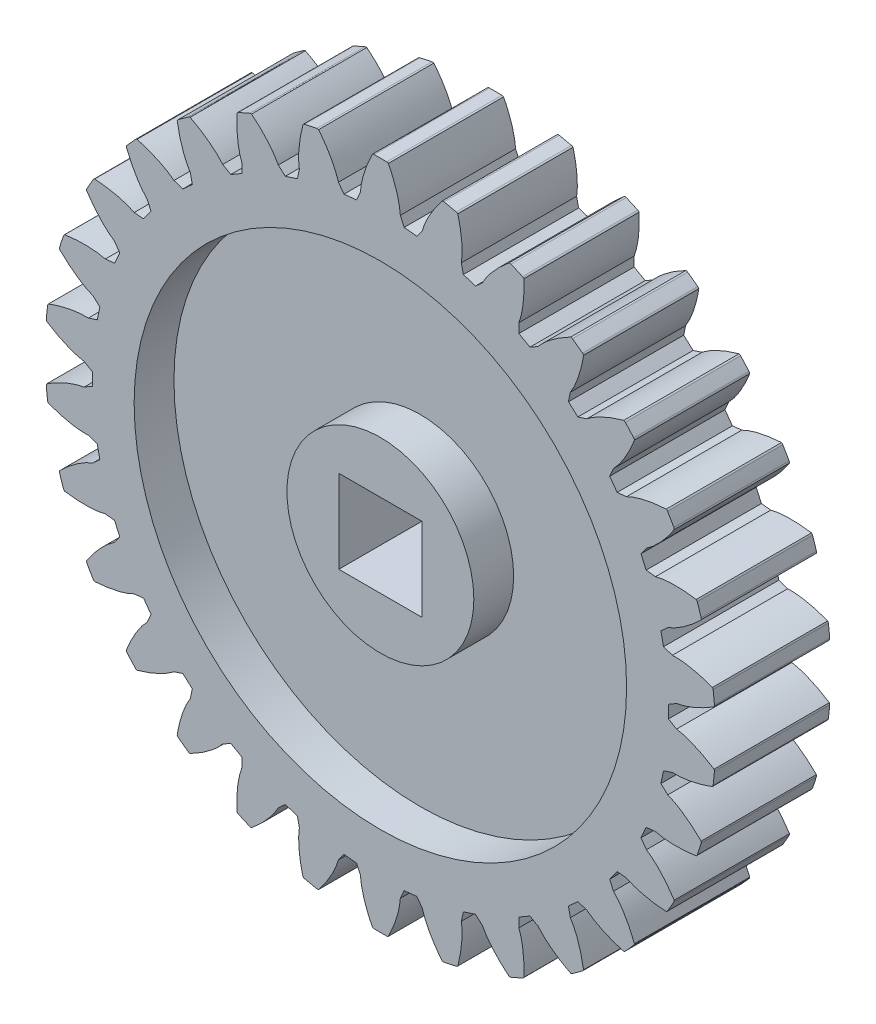
SolidWorks part; units mm, degrees
material "Nylon 101"
ref_plane "Front Plane" through (0, 0, 0) normal (0, 0, 1) x (1, 0, 0)
ref_plane "Top Plane" through (0, 0, 0) normal (0, 1, 0) x (1, 0, 0)
ref_plane "Right Plane" through (0, 0, 0) normal (1, 0, 0) x (0, 0, -1)
ref_axis "Axis1" through (0, 0, -3.2875) along (0, 0, 1)
sketch "Sketch1" plane through (0, 0, 0) normal (0, 0, 1) x (1, 0, 0)
  arc A0 (3.6196, 15.5852) -> (3.0324, 15.71) centre (0, 0) ccw
  arc A1 (0.3001, 15.9972) -> (-0.3001, 15.9972) centre (0, 0) ccw
  arc A2 (-3.0324, 15.71) -> (-3.6196, 15.5852) centre (0, 0) ccw
  arc A3 (-6.2325, 14.7362) -> (-6.7808, 14.4921) centre (0, 0) ccw
  arc A4 (-9.1601, 13.1184) -> (-9.6457, 12.7656) centre (0, 0) ccw
  arc A5 (-11.6874, 10.9272) -> (-12.089, 10.4812) centre (0, 0) ccw
  arc A6 (-13.7039, 8.2585) -> (-14.004, 7.7387) centre (0, 0) ccw
  arc A7 (-15.1215, 5.2288) -> (-15.307, 4.658) centre (0, 0) ccw
  arc A8 (-15.8782, 1.9706) -> (-15.9409, 1.3737) centre (0, 0) ccw
  arc A9 (-15.9409, -1.3737) -> (-15.8782, -1.9706) centre (0, 0) ccw
  arc A10 (-15.307, -4.658) -> (-15.1215, -5.2288) centre (0, 0) ccw
  arc A11 (-14.004, -7.7387) -> (-13.7039, -8.2585) centre (0, 0) ccw
  arc A12 (-12.089, -10.4812) -> (-11.6874, -10.9272) centre (0, 0) ccw
  arc A13 (-9.6457, -12.7656) -> (-9.1601, -13.1184) centre (0, 0) ccw
  arc A14 (-6.7808, -14.4921) -> (-6.2325, -14.7362) centre (0, 0) ccw
  arc A15 (-3.6196, -15.5852) -> (-3.0324, -15.71) centre (0, 0) ccw
  arc A16 (-0.3001, -15.9972) -> (0.3001, -15.9972) centre (0, 0) ccw
  arc A17 (3.0324, -15.71) -> (3.6196, -15.5852) centre (0, 0) ccw
  arc A18 (6.2325, -14.7362) -> (6.7808, -14.4921) centre (0, 0) ccw
  arc A19 (9.1601, -13.1184) -> (9.6457, -12.7656) centre (0, 0) ccw
  arc A20 (11.6874, -10.9272) -> (12.089, -10.4812) centre (0, 0) ccw
  arc A21 (13.7039, -8.2585) -> (14.004, -7.7387) centre (0, 0) ccw
  arc A22 (15.1215, -5.2288) -> (15.307, -4.658) centre (0, 0) ccw
  arc A23 (15.8782, -1.9706) -> (15.9409, -1.3737) centre (0, 0) ccw
  arc A24 (15.9409, 1.3737) -> (15.8782, 1.9706) centre (0, 0) ccw
  arc A25 (15.307, 4.658) -> (15.1215, 5.2288) centre (0, 0) ccw
  arc A26 (14.004, 7.7387) -> (13.7039, 8.2585) centre (0, 0) ccw
  arc A27 (12.089, 10.4812) -> (11.6874, 10.9272) centre (0, 0) ccw
  arc A28 (9.6457, 12.7656) -> (9.1601, 13.1184) centre (0, 0) ccw
  arc A29 (6.7808, 14.4921) -> (6.2325, 14.7362) centre (0, 0) ccw
  spline S0 degree 2 poles (3.6196, 15.5852) (3.6647, 15.5747) (3.6932, 15.5435) knots 0 0 0 1 1 1
  spline S1 degree 2 poles (2.9482, 15.7019) (2.9869, 15.7188) (3.0324, 15.71) knots 0 0 0 1 1 1
  spline S2 degree 2 poles (2.0027, 14.0013) (2.021, 14.0609) (2.0394, 14.1205) (2.1444, 14.4615) (2.6134, 15.2842) (2.9482, 15.7019) knots -0.082148 -0.082148 -0.082148 0 0 0.469989 0.94695 0.94695 0.94695
  spline S3 degree 2 poles (1.7379, 13.6408) (1.799, 13.7255) (1.8601, 13.8102) (1.9057, 13.8734) (1.9535, 13.9364) (1.9781, 13.9689) (2.0027, 14.0013) knots -1.340212 -1.340212 -1.340212 0 0 1 1 1.515233 1.515233 1.515233
  spline S4 degree 2 poles (1.1362, 13.7041) (1.2218, 13.6959) (1.3075, 13.6877) (1.4373, 13.6753) (1.5669, 13.6604) (1.6524, 13.6506) (1.7379, 13.6408) knots -0.659931 -0.659931 -0.659931 0 0 1 1 1.659931 1.659931 1.659931
  spline S5 degree 2 poles (0.9521, 14.1118) (0.9694, 14.0749) (0.9867, 14.038) (1.0203, 13.9665) (1.0518, 13.8952) (1.094, 13.7996) (1.1362, 13.7041) knots -0.515233 -0.515233 -0.515233 0 0 1 1 2.340212 2.340212 2.340212
  spline S6 degree 2 poles (0.3808, 15.9717) (0.7214, 15.2951) (0.9228, 14.4394) (0.941, 14.236) (0.9466, 14.1739) (0.9521, 14.1118) knots 0 0 0 0.627513 0.879079 0.879079 0.955892 0.955892 0.955892
  spline S7 degree 2 poles (0.3001, 15.9972) (0.3465, 15.9963) (0.3808, 15.9717) knots 0 0 0 1 1 1
  spline S8 degree 2 poles (-0.3808, 15.9717) (-0.3465, 15.9963) (-0.3001, 15.9972) knots 0 0 0 1 1 1
  spline S9 degree 2 poles (-0.9521, 14.1118) (-0.9466, 14.1739) (-0.941, 14.236) (-0.9092, 14.5914) (-0.6215, 15.4935) (-0.3808, 15.9717) knots -0.082148 -0.082148 -0.082148 0 0 0.469989 0.94695 0.94695 0.94695
  spline S10 degree 2 poles (-1.1362, 13.7041) (-1.094, 13.7996) (-1.0518, 13.8952) (-1.0203, 13.9665) (-0.9867, 14.038) (-0.9694, 14.0749) (-0.9521, 14.1118) knots -1.340212 -1.340212 -1.340212 0 0 1 1 1.515233 1.515233 1.515233
  spline S11 degree 2 poles (-1.7379, 13.6408) (-1.6524, 13.6506) (-1.5669, 13.6604) (-1.4373, 13.6753) (-1.3075, 13.6877) (-1.2218, 13.6959) (-1.1362, 13.7041) knots -0.659931 -0.659931 -0.659931 0 0 1 1 1.659931 1.659931 1.659931
  spline S12 degree 2 poles (-2.0027, 14.0013) (-1.9781, 13.9689) (-1.9535, 13.9364) (-1.9057, 13.8734) (-1.8601, 13.8102) (-1.799, 13.7255) (-1.7379, 13.6408) knots -0.515233 -0.515233 -0.515233 0 0 1 1 2.340212 2.340212 2.340212
  spline S13 degree 2 poles (-2.9482, 15.7019) (-2.4744, 15.1108) (-2.0995, 14.3157) (-2.0394, 14.1205) (-2.021, 14.0609) (-2.0027, 14.0013) knots 0 0 0 0.627513 0.879079 0.879079 0.955892 0.955892 0.955892
  spline S14 degree 2 poles (-3.0324, 15.71) (-2.9869, 15.7188) (-2.9482, 15.7019) knots 0 0 0 1 1 1
  spline S15 degree 2 poles (-3.6932, 15.5435) (-3.6647, 15.5747) (-3.6196, 15.5852) knots 0 0 0 1 1 1
  spline S16 degree 2 poles (-3.8653, 13.6054) (-3.8728, 13.6673) (-3.8803, 13.7292) (-3.923, 14.0835) (-3.8292, 15.0258) (-3.6932, 15.5435) knots -0.082148 -0.082148 -0.082148 0 0 0.469989 0.94695 0.94695 0.94695
  spline S17 degree 2 poles (-3.9606, 13.1684) (-3.9392, 13.2706) (-3.9178, 13.3728) (-3.9018, 13.4491) (-3.8839, 13.5261) (-3.8746, 13.5658) (-3.8653, 13.6054) knots -1.340212 -1.340212 -1.340212 0 0 1 1 1.515233 1.515233 1.515233
  spline S18 degree 2 poles (-4.536, 12.9814) (-4.4544, 13.0088) (-4.3728, 13.0361) (-4.2492, 13.0776) (-4.1248, 13.1167) (-4.0427, 13.1426) (-3.9606, 13.1684) knots -0.659931 -0.659931 -0.659931 0 0 1 1 1.659931 1.659931 1.659931
  spline S19 degree 2 poles (-4.87, 13.279) (-4.8392, 13.2524) (-4.8083, 13.2257) (-4.7485, 13.174) (-4.6908, 13.1217) (-4.6134, 13.0515) (-4.536, 12.9814) knots -0.515233 -0.515233 -0.515233 0 0 1 1 2.340212 2.340212 2.340212
  spline S20 degree 2 poles (-6.1484, 14.7458) (-5.5621, 14.2662) (-5.03, 13.5664) (-4.9306, 13.388) (-4.9003, 13.3335) (-4.87, 13.279) knots 0 0 0 0.627513 0.879079 0.879079 0.955892 0.955892 0.955892
  spline S21 degree 2 poles (-6.2325, 14.7362) (-6.1897, 14.7543) (-6.1484, 14.7458) knots 0 0 0 1 1 1
  spline S22 degree 2 poles (-6.8442, 14.436) (-6.8228, 14.4724) (-6.7808, 14.4921) knots 0 0 0 1 1 1
  spline S23 degree 2 poles (-6.6096, 12.5045) (-6.6298, 12.5635) (-6.6499, 12.6225) (-6.7654, 12.9601) (-6.8695, 13.9013) (-6.8442, 14.436) knots -0.082148 -0.082148 -0.082148 0 0 0.469989 0.94695 0.94695 0.94695
  spline S24 degree 2 poles (-6.6119, 12.0572) (-6.6122, 12.1616) (-6.6126, 12.2661) (-6.6128, 12.344) (-6.6112, 12.423) (-6.6104, 12.4637) (-6.6096, 12.5045) knots -1.340212 -1.340212 -1.340212 0 0 1 1 1.515233 1.515233 1.515233
  spline S25 degree 2 poles (-7.1359, 11.7546) (-7.0617, 11.7984) (-6.9876, 11.8421) (-6.8753, 11.9084) (-6.7618, 11.9725) (-6.6868, 12.0148) (-6.6119, 12.0572) knots -0.659931 -0.659931 -0.659931 0 0 1 1 1.659931 1.659931 1.659931
  spline S26 degree 2 poles (-7.5244, 11.9763) (-7.4887, 11.9566) (-7.453, 11.937) (-7.3838, 11.8989) (-7.3164, 11.8597) (-7.2262, 11.8072) (-7.1359, 11.7546) knots -0.515233 -0.515233 -0.515233 0 0 1 1 2.340212 2.340212 2.340212
  spline S27 degree 2 poles (-9.0799, 13.1452) (-8.4066, 12.798) (-7.7407, 12.2241) (-7.6064, 12.0703) (-7.5654, 12.0233) (-7.5244, 11.9763) knots 0 0 0 0.627513 0.879079 0.879079 0.955892 0.955892 0.955892
  spline S28 degree 2 poles (-9.1601, 13.1184) (-9.1221, 13.145) (-9.0799, 13.1452) knots 0 0 0 1 1 1
  spline S29 degree 2 poles (-9.696, 12.6976) (-9.6827, 12.7376) (-9.6457, 12.7656) knots 0 0 0 1 1 1
  spline S30 degree 2 poles (-9.065, 10.857) (-9.097, 10.9105) (-9.129, 10.964) (-9.3121, 11.2702) (-9.6097, 12.1692) (-9.696, 12.6976) knots -0.082148 -0.082148 -0.082148 0 0 0.469989 0.94695 0.94695 0.94695
  spline S31 degree 2 poles (-8.9742, 10.419) (-8.9963, 10.5211) (-9.0183, 10.6232) (-9.0348, 10.6994) (-9.0496, 10.777) (-9.0573, 10.817) (-9.065, 10.857) knots -1.340212 -1.340212 -1.340212 0 0 1 1 1.515233 1.515233 1.515233
  spline S32 degree 2 poles (-9.4239, 10.0141) (-9.3605, 10.0723) (-9.297, 10.1305) (-9.201, 10.2187) (-9.1032, 10.305) (-9.0387, 10.362) (-8.9742, 10.419) knots -0.659931 -0.659931 -0.659931 0 0 1 1 1.659931 1.659931 1.659931
  spline S33 degree 2 poles (-9.85, 10.1502) (-9.811, 10.1384) (-9.772, 10.1266) (-9.6964, 10.1037) (-9.6223, 10.0793) (-9.5231, 10.0467) (-9.4239, 10.0141) knots -0.515233 -0.515233 -0.515233 0 0 1 1 2.340212 2.340212 2.340212
  spline S34 degree 2 poles (-11.6145, 10.9702) (-10.8838, 10.7705) (-10.1131, 10.3476) (-9.9497, 10.225) (-9.8999, 10.1876) (-9.85, 10.1502) knots 0 0 0 0.627513 0.879079 0.879079 0.955892 0.955892 0.955892
  spline S35 degree 2 poles (-11.6874, 10.9272) (-11.6557, 10.9611) (-11.6145, 10.9702) knots 0 0 0 1 1 1
  spline S36 degree 2 poles (-12.1241, 10.4042) (-12.1194, 10.4461) (-12.089, 10.4812) knots 0 0 0 1 1 1
  spline S37 degree 2 poles (-11.1242, 8.735) (-11.1666, 8.7807) (-11.209, 8.8264) (-11.4519, 9.0879) (-11.9298, 9.9053) (-12.1241, 10.4042) knots -0.082148 -0.082148 -0.082148 0 0 0.469989 0.94695 0.94695 0.94695
  spline S38 degree 2 poles (-10.9443, 8.3255) (-10.9871, 8.4207) (-11.0299, 8.516) (-11.0619, 8.5871) (-11.0925, 8.66) (-11.1084, 8.6975) (-11.1242, 8.735) knots -1.340212 -1.340212 -1.340212 0 0 1 1 1.515233 1.515233 1.515233
  spline S39 degree 2 poles (-11.3, 7.836) (-11.2501, 7.9061) (-11.2001, 7.9762) (-11.1245, 8.0824) (-11.0468, 8.1872) (-10.9956, 8.2563) (-10.9443, 8.3255) knots -0.659931 -0.659931 -0.659931 0 0 1 1 1.659931 1.659931 1.659931
  spline S40 degree 2 poles (-11.7451, 7.8804) (-11.7045, 7.877) (-11.6639, 7.8736) (-11.5851, 7.8669) (-11.5077, 7.8585) (-11.4038, 7.8472) (-11.3, 7.836) knots -0.515233 -0.515233 -0.515233 0 0 1 1 2.340212 2.340212 2.340212
  spline S41 degree 2 poles (-13.6415, 8.3157) (-12.8853, 8.2723) (-12.0435, 8.0189) (-11.8582, 7.9329) (-11.8016, 7.9067) (-11.7451, 7.8804) knots 0 0 0 0.627513 0.879079 0.879079 0.955892 0.955892 0.955892
  spline S42 degree 2 poles (-13.7039, 8.2585) (-13.68, 8.2982) (-13.6415, 8.3157) knots 0 0 0 1 1 1
  spline S43 degree 2 poles (-14.0223, 7.6561) (-14.0265, 7.6981) (-14.004, 7.7387) knots 0 0 0 1 1 1
  spline S44 degree 2 poles (-12.6972, 6.2313) (-12.7482, 6.2672) (-12.7992, 6.3031) (-13.0911, 6.5083) (-13.7285, 7.2085) (-14.0223, 7.6561) knots -0.082148 -0.082148 -0.082148 0 0 0.469989 0.94695 0.94695 0.94695
  spline S45 degree 2 poles (-12.4361, 5.8681) (-12.4978, 5.9524) (-12.5595, 6.0367) (-12.6055, 6.0996) (-12.6507, 6.1645) (-12.6739, 6.1979) (-12.6972, 6.2313) knots -1.340212 -1.340212 -1.340212 0 0 1 1 1.515233 1.515233 1.515233
  spline S46 degree 2 poles (-12.6822, 5.3153) (-12.648, 5.3943) (-12.6137, 5.4732) (-12.5618, 5.5929) (-12.5076, 5.7115) (-12.4719, 5.7898) (-12.4361, 5.8681) knots -0.659931 -0.659931 -0.659931 0 0 1 1 1.659931 1.659931 1.659931
  spline S47 degree 2 poles (-13.1269, 5.2663) (-13.0864, 5.2714) (-13.046, 5.2764) (-12.9676, 5.2863) (-12.8901, 5.2942) (-12.7861, 5.3048) (-12.6822, 5.3153) knots -0.515233 -0.515233 -0.515233 0 0 1 1 2.340212 2.340212 2.340212
  spline S48 degree 2 poles (-15.0723, 5.2977) (-14.3236, 5.4125) (-13.4475, 5.3396) (-13.2484, 5.2941) (-13.1876, 5.2802) (-13.1269, 5.2663) knots 0 0 0 0.627513 0.879079 0.879079 0.955892 0.955892 0.955892
  spline S49 degree 2 poles (-15.1215, 5.2288) (-15.1063, 5.2727) (-15.0723, 5.2977) knots 0 0 0 1 1 1
  spline S50 degree 2 poles (-15.3077, 4.5734) (-15.3205, 4.6136) (-15.307, 4.658) knots 0 0 0 1 1 1
  spline S51 degree 2 poles (-13.7153, 3.4553) (-13.7727, 3.4797) (-13.83, 3.5042) (-14.1582, 3.6443) (-14.9273, 4.1967) (-15.3077, 4.5734) knots -0.082148 -0.082148 -0.082148 0 0 0.469989 0.94695 0.94695 0.94695
  spline S52 degree 2 poles (-13.3844, 3.1542) (-13.4623, 3.2239) (-13.5401, 3.2935) (-13.5982, 3.3455) (-13.6559, 3.3995) (-13.6856, 3.4274) (-13.7153, 3.4553) knots -1.340212 -1.340212 -1.340212 0 0 1 1 1.515233 1.515233 1.515233
  spline S53 degree 2 poles (-13.5102, 2.5624) (-13.4931, 2.6468) (-13.476, 2.7311) (-13.4501, 2.8589) (-13.4218, 2.9862) (-13.4031, 3.0702) (-13.3844, 3.1542) knots -0.659931 -0.659931 -0.659931 0 0 1 1 1.659931 1.659931 1.659931
  spline S54 degree 2 poles (-13.9349, 2.422) (-13.8964, 2.4353) (-13.858, 2.4487) (-13.7833, 2.4747) (-13.7091, 2.4985) (-13.6097, 2.5305) (-13.5102, 2.5624) knots -0.515233 -0.515233 -0.515233 0 0 1 1 2.340212 2.340212 2.340212
  spline S55 degree 2 poles (-15.8444, 2.0482) (-15.1359, 2.3162) (-14.2639, 2.4271) (-14.0596, 2.4239) (-13.9973, 2.4229) (-13.9349, 2.422) knots 0 0 0 0.627513 0.879079 0.879079 0.955892 0.955892 0.955892
  spline S56 degree 2 poles (-15.8782, 1.9706) (-15.8725, 2.0167) (-15.8444, 2.0482) knots 0 0 0 1 1 1
  spline S57 degree 2 poles (-15.924, 1.2908) (-15.9449, 1.3275) (-15.9409, 1.3737) knots 0 0 0 1 1 1
  spline S58 degree 2 poles (-14.134, 0.5282) (-14.1952, 0.5402) (-14.2564, 0.5522) (-14.6065, 0.621) (-15.4736, 1.0014) (-15.924, 1.2908) knots -0.082148 -0.082148 -0.082148 0 0 0.469989 0.94695 0.94695 0.94695
  spline S59 degree 2 poles (-13.7477, 0.3025) (-13.8384, 0.3545) (-13.929, 0.4064) (-13.9966, 0.4451) (-14.0643, 0.486) (-14.0991, 0.5071) (-14.134, 0.5282) knots -1.340212 -1.340212 -1.340212 0 0 1 1 1.515233 1.515233 1.515233
  spline S60 degree 2 poles (-13.7477, -0.3025) (-13.7486, -0.2165) (-13.7494, -0.1304) (-13.7506, 0) (-13.7494, 0.1304) (-13.7486, 0.2165) (-13.7477, 0.3025) knots -0.659931 -0.659931 -0.659931 0 0 1 1 1.659931 1.659931 1.659931
  spline S61 degree 2 poles (-14.134, -0.5282) (-14.0991, -0.5071) (-14.0643, -0.486) (-13.9966, -0.4451) (-13.929, -0.4064) (-13.8384, -0.3545) (-13.7477, -0.3025) knots -0.515233 -0.515233 -0.515233 0 0 1 1 2.340212 2.340212 2.340212
  spline S62 degree 2 poles (-15.924, -1.2908) (-15.2867, -0.8814) (-14.4568, -0.5916) (-14.2564, -0.5522) (-14.1952, -0.5402) (-14.134, -0.5282) knots 0 0 0 0.627513 0.879079 0.879079 0.955892 0.955892 0.955892
  spline S63 degree 2 poles (-15.9409, -1.3737) (-15.9449, -1.3275) (-15.924, -1.2908) knots 0 0 0 1 1 1
  spline S64 degree 2 poles (-15.8444, -2.0482) (-15.8725, -2.0167) (-15.8782, -1.9706) knots 0 0 0 1 1 1
  spline S65 degree 2 poles (-13.9349, -2.422) (-13.9973, -2.4229) (-14.0596, -2.4239) (-14.4164, -2.4294) (-15.3437, -2.2376) (-15.8444, -2.0482) knots -0.082148 -0.082148 -0.082148 0 0 0.469989 0.94695 0.94695 0.94695
  spline S66 degree 2 poles (-13.5102, -2.5624) (-13.6097, -2.5305) (-13.7091, -2.4985) (-13.7833, -2.4747) (-13.858, -2.4487) (-13.8964, -2.4353) (-13.9349, -2.422) knots -1.340212 -1.340212 -1.340212 0 0 1 1 1.515233 1.515233 1.515233
  spline S67 degree 2 poles (-13.3844, -3.1542) (-13.4031, -3.0702) (-13.4218, -2.9862) (-13.4501, -2.8589) (-13.476, -2.7311) (-13.4931, -2.6468) (-13.5102, -2.5624) knots -0.659931 -0.659931 -0.659931 0 0 1 1 1.659931 1.659931 1.659931
  spline S68 degree 2 poles (-13.7153, -3.4553) (-13.6856, -3.4274) (-13.6559, -3.3995) (-13.5982, -3.3455) (-13.5401, -3.2935) (-13.4623, -3.2239) (-13.3844, -3.1542) knots -0.515233 -0.515233 -0.515233 0 0 1 1 2.340212 2.340212 2.340212
  spline S69 degree 2 poles (-15.3077, -4.5734) (-14.7694, -4.0404) (-14.0179, -3.5844) (-13.83, -3.5042) (-13.7727, -3.4797) (-13.7153, -3.4553) knots 0 0 0 0.627513 0.879079 0.879079 0.955892 0.955892 0.955892
  spline S70 degree 2 poles (-15.307, -4.658) (-15.3205, -4.6136) (-15.3077, -4.5734) knots 0 0 0 1 1 1
  spline S71 degree 2 poles (-15.0723, -5.2977) (-15.1063, -5.2727) (-15.1215, -5.2288) knots 0 0 0 1 1 1
  spline S72 degree 2 poles (-13.1269, -5.2663) (-13.1876, -5.2802) (-13.2484, -5.2941) (-13.5962, -5.3737) (-14.5432, -5.3788) (-15.0723, -5.2977) knots -0.082148 -0.082148 -0.082148 0 0 0.469989 0.94695 0.94695 0.94695
  spline S73 degree 2 poles (-12.6822, -5.3153) (-12.7861, -5.3048) (-12.8901, -5.2942) (-12.9676, -5.2863) (-13.046, -5.2764) (-13.0864, -5.2714) (-13.1269, -5.2663) knots -1.340212 -1.340212 -1.340212 0 0 1 1 1.515233 1.515233 1.515233
  spline S74 degree 2 poles (-12.4361, -5.8681) (-12.4719, -5.7898) (-12.5076, -5.7115) (-12.5618, -5.5929) (-12.6137, -5.4732) (-12.648, -5.3943) (-12.6822, -5.3153) knots -0.659931 -0.659931 -0.659931 0 0 1 1 1.659931 1.659931 1.659931
  spline S75 degree 2 poles (-12.6972, -6.2313) (-12.6739, -6.1979) (-12.6507, -6.1645) (-12.6055, -6.0996) (-12.5595, -6.0367) (-12.4978, -5.9524) (-12.4361, -5.8681) knots -0.515233 -0.515233 -0.515233 0 0 1 1 2.340212 2.340212 2.340212
  spline S76 degree 2 poles (-14.0223, -7.6561) (-13.6066, -7.0228) (-12.9663, -6.4205) (-12.7992, -6.3031) (-12.7482, -6.2672) (-12.6972, -6.2313) knots 0 0 0 0.627513 0.879079 0.879079 0.955892 0.955892 0.955892
  spline S77 degree 2 poles (-14.004, -7.7387) (-14.0265, -7.6981) (-14.0223, -7.6561) knots 0 0 0 1 1 1
  spline S78 degree 2 poles (-13.6415, -8.3157) (-13.68, -8.2982) (-13.7039, -8.2585) knots 0 0 0 1 1 1
  spline S79 degree 2 poles (-11.7451, -7.8804) (-11.8016, -7.9067) (-11.8582, -7.9329) (-12.1819, -8.0831) (-13.1071, -8.285) (-13.6415, -8.3157) knots -0.082148 -0.082148 -0.082148 0 0 0.469989 0.94695 0.94695 0.94695
  spline S80 degree 2 poles (-11.3, -7.836) (-11.4038, -7.8472) (-11.5077, -7.8585) (-11.5851, -7.8669) (-11.6639, -7.8736) (-11.7045, -7.877) (-11.7451, -7.8804) knots -1.340212 -1.340212 -1.340212 0 0 1 1 1.515233 1.515233 1.515233
  spline S81 degree 2 poles (-10.9443, -8.3255) (-10.9956, -8.2563) (-11.0468, -8.1872) (-11.1245, -8.0824) (-11.2001, -7.9762) (-11.2501, -7.9061) (-11.3, -7.836) knots -0.659931 -0.659931 -0.659931 0 0 1 1 1.659931 1.659931 1.659931
  spline S82 degree 2 poles (-11.1242, -8.735) (-11.1084, -8.6975) (-11.0925, -8.66) (-11.0619, -8.5871) (-11.0299, -8.516) (-10.9871, -8.4207) (-10.9443, -8.3255) knots -0.515233 -0.515233 -0.515233 0 0 1 1 2.340212 2.340212 2.340212
  spline S83 degree 2 poles (-12.1241, -10.4042) (-11.8492, -9.6983) (-11.348, -8.9761) (-11.209, -8.8264) (-11.1666, -8.7807) (-11.1242, -8.735) knots 0 0 0 0.627513 0.879079 0.879079 0.955892 0.955892 0.955892
  spline S84 degree 2 poles (-12.089, -10.4812) (-12.1194, -10.4461) (-12.1241, -10.4042) knots 0 0 0 1 1 1
  spline S85 degree 2 poles (-11.6145, -10.9702) (-11.6557, -10.9611) (-11.6874, -10.9272) knots 0 0 0 1 1 1
  spline S86 degree 2 poles (-9.85, -10.1502) (-9.8999, -10.1876) (-9.9497, -10.225) (-10.2351, -10.4392) (-11.0981, -10.8291) (-11.6145, -10.9702) knots -0.082148 -0.082148 -0.082148 0 0 0.469989 0.94695 0.94695 0.94695
  spline S87 degree 2 poles (-9.4239, -10.0141) (-9.5231, -10.0467) (-9.6223, -10.0793) (-9.6964, -10.1037) (-9.772, -10.1266) (-9.811, -10.1384) (-9.85, -10.1502) knots -1.340212 -1.340212 -1.340212 0 0 1 1 1.515233 1.515233 1.515233
  spline S88 degree 2 poles (-8.9742, -10.419) (-9.0387, -10.362) (-9.1032, -10.305) (-9.201, -10.2187) (-9.297, -10.1305) (-9.3605, -10.0723) (-9.4239, -10.0141) knots -0.659931 -0.659931 -0.659931 0 0 1 1 1.659931 1.659931 1.659931
  spline S89 degree 2 poles (-9.065, -10.857) (-9.0573, -10.817) (-9.0496, -10.777) (-9.0348, -10.6994) (-9.0183, -10.6232) (-8.9963, -10.5211) (-8.9742, -10.419) knots -0.515233 -0.515233 -0.515233 0 0 1 1 2.340212 2.340212 2.340212
  spline S90 degree 2 poles (-9.696, -12.6976) (-9.5738, -11.95) (-9.2338, -11.1393) (-9.129, -10.964) (-9.097, -10.9105) (-9.065, -10.857) knots 0 0 0 0.627513 0.879079 0.879079 0.955892 0.955892 0.955892
  spline S91 degree 2 poles (-9.6457, -12.7656) (-9.6827, -12.7376) (-9.696, -12.6976) knots 0 0 0 1 1 1
  spline S92 degree 2 poles (-9.0799, -13.1452) (-9.1221, -13.145) (-9.1601, -13.1184) knots 0 0 0 1 1 1
  spline S93 degree 2 poles (-7.5244, -11.9763) (-7.5654, -12.0233) (-7.6064, -12.0703) (-7.841, -12.3391) (-8.6041, -12.8998) (-9.0799, -13.1452) knots -0.082148 -0.082148 -0.082148 0 0 0.469989 0.94695 0.94695 0.94695
  spline S94 degree 2 poles (-7.1359, -11.7546) (-7.2262, -11.8072) (-7.3164, -11.8597) (-7.3838, -11.8989) (-7.453, -11.937) (-7.4887, -11.9566) (-7.5244, -11.9763) knots -1.340212 -1.340212 -1.340212 0 0 1 1 1.515233 1.515233 1.515233
  spline S95 degree 2 poles (-6.6119, -12.0572) (-6.6868, -12.0148) (-6.7618, -11.9725) (-6.8753, -11.9084) (-6.9876, -11.8421) (-7.0617, -11.7984) (-7.1359, -11.7546) knots -0.659931 -0.659931 -0.659931 0 0 1 1 1.659931 1.659931 1.659931
  spline S96 degree 2 poles (-6.6096, -12.5045) (-6.6104, -12.4637) (-6.6112, -12.423) (-6.6128, -12.344) (-6.6126, -12.2661) (-6.6122, -12.1616) (-6.6119, -12.0572) knots -0.515233 -0.515233 -0.515233 0 0 1 1 2.340212 2.340212 2.340212
  spline S97 degree 2 poles (-6.8442, -14.436) (-6.8801, -13.6794) (-6.716, -12.8157) (-6.6499, -12.6225) (-6.6298, -12.5635) (-6.6096, -12.5045) knots 0 0 0 0.627513 0.879079 0.879079 0.955892 0.955892 0.955892
  spline S98 degree 2 poles (-6.7808, -14.4921) (-6.8228, -14.4724) (-6.8442, -14.436) knots 0 0 0 1 1 1
  spline S99 degree 2 poles (-6.1484, -14.7458) (-6.1897, -14.7543) (-6.2325, -14.7362) knots 0 0 0 1 1 1
  spline S100 degree 2 poles (-4.87, -13.279) (-4.9003, -13.3335) (-4.9306, -13.388) (-5.1043, -13.6997) (-5.734, -14.4068) (-6.1484, -14.7458) knots -0.082148 -0.082148 -0.082148 0 0 0.469989 0.94695 0.94695 0.94695
  spline S101 degree 2 poles (-4.536, -12.9814) (-4.6134, -13.0515) (-4.6908, -13.1217) (-4.7485, -13.174) (-4.8083, -13.2257) (-4.8392, -13.2524) (-4.87, -13.279) knots -1.340212 -1.340212 -1.340212 0 0 1 1 1.515233 1.515233 1.515233
  spline S102 degree 2 poles (-3.9606, -13.1684) (-4.0427, -13.1426) (-4.1248, -13.1167) (-4.2492, -13.0776) (-4.3728, -13.0361) (-4.4544, -13.0088) (-4.536, -12.9814) knots -0.659931 -0.659931 -0.659931 0 0 1 1 1.659931 1.659931 1.659931
  spline S103 degree 2 poles (-3.8653, -13.6054) (-3.8746, -13.5658) (-3.8839, -13.5261) (-3.9018, -13.4491) (-3.9178, -13.3728) (-3.9392, -13.2706) (-3.9606, -13.1684) knots -0.515233 -0.515233 -0.515233 0 0 1 1 2.340212 2.340212 2.340212
  spline S104 degree 2 poles (-3.6932, -15.5435) (-3.8856, -14.8109) (-3.9047, -13.932) (-3.8803, -13.7292) (-3.8728, -13.6673) (-3.8653, -13.6054) knots 0 0 0 0.627513 0.879079 0.879079 0.955892 0.955892 0.955892
  spline S105 degree 2 poles (-3.6196, -15.5852) (-3.6647, -15.5747) (-3.6932, -15.5435) knots 0 0 0 1 1 1
  spline S106 degree 2 poles (-2.9482, -15.7019) (-2.9869, -15.7188) (-3.0324, -15.71) knots 0 0 0 1 1 1
  spline S107 degree 2 poles (-2.0027, -14.0013) (-2.021, -14.0609) (-2.0394, -14.1205) (-2.1444, -14.4615) (-2.6134, -15.2842) (-2.9482, -15.7019) knots -0.082148 -0.082148 -0.082148 0 0 0.469989 0.94695 0.94695 0.94695
  spline S108 degree 2 poles (-1.7379, -13.6408) (-1.799, -13.7255) (-1.8601, -13.8102) (-1.9057, -13.8734) (-1.9535, -13.9364) (-1.9781, -13.9689) (-2.0027, -14.0013) knots -1.340212 -1.340212 -1.340212 0 0 1 1 1.515233 1.515233 1.515233
  spline S109 degree 2 poles (-1.1362, -13.7041) (-1.2218, -13.6959) (-1.3075, -13.6877) (-1.4373, -13.6753) (-1.5669, -13.6604) (-1.6524, -13.6506) (-1.7379, -13.6408) knots -0.659931 -0.659931 -0.659931 0 0 1 1 1.659931 1.659931 1.659931
  spline S110 degree 2 poles (-0.9521, -14.1118) (-0.9694, -14.0749) (-0.9867, -14.038) (-1.0203, -13.9665) (-1.0518, -13.8952) (-1.094, -13.7996) (-1.1362, -13.7041) knots -0.515233 -0.515233 -0.515233 0 0 1 1 2.340212 2.340212 2.340212
  spline S111 degree 2 poles (-0.3808, -15.9717) (-0.7214, -15.2951) (-0.9228, -14.4394) (-0.941, -14.236) (-0.9466, -14.1739) (-0.9521, -14.1118) knots 0 0 0 0.627513 0.879079 0.879079 0.955892 0.955892 0.955892
  spline S112 degree 2 poles (-0.3001, -15.9972) (-0.3465, -15.9963) (-0.3808, -15.9717) knots 0 0 0 1 1 1
  spline S113 degree 2 poles (0.3808, -15.9717) (0.3465, -15.9963) (0.3001, -15.9972) knots 0 0 0 1 1 1
  spline S114 degree 2 poles (0.9521, -14.1118) (0.9466, -14.1739) (0.941, -14.236) (0.9092, -14.5914) (0.6215, -15.4935) (0.3808, -15.9717) knots -0.082148 -0.082148 -0.082148 0 0 0.469989 0.94695 0.94695 0.94695
  spline S115 degree 2 poles (1.1362, -13.7041) (1.094, -13.7996) (1.0518, -13.8952) (1.0203, -13.9665) (0.9867, -14.038) (0.9694, -14.0749) (0.9521, -14.1118) knots -1.340212 -1.340212 -1.340212 0 0 1 1 1.515233 1.515233 1.515233
  spline S116 degree 2 poles (1.7379, -13.6408) (1.6524, -13.6506) (1.5669, -13.6604) (1.4373, -13.6753) (1.3075, -13.6877) (1.2218, -13.6959) (1.1362, -13.7041) knots -0.659931 -0.659931 -0.659931 0 0 1 1 1.659931 1.659931 1.659931
  spline S117 degree 2 poles (2.0027, -14.0013) (1.9781, -13.9689) (1.9535, -13.9364) (1.9057, -13.8734) (1.8601, -13.8102) (1.799, -13.7255) (1.7379, -13.6408) knots -0.515233 -0.515233 -0.515233 0 0 1 1 2.340212 2.340212 2.340212
  spline S118 degree 2 poles (2.9482, -15.7019) (2.4744, -15.1108) (2.0995, -14.3157) (2.0394, -14.1205) (2.021, -14.0609) (2.0027, -14.0013) knots 0 0 0 0.627513 0.879079 0.879079 0.955892 0.955892 0.955892
  spline S119 degree 2 poles (3.0324, -15.71) (2.9869, -15.7188) (2.9482, -15.7019) knots 0 0 0 1 1 1
  spline S120 degree 2 poles (3.6932, -15.5435) (3.6647, -15.5747) (3.6196, -15.5852) knots 0 0 0 1 1 1
  spline S121 degree 2 poles (3.8653, -13.6054) (3.8728, -13.6673) (3.8803, -13.7292) (3.923, -14.0835) (3.8292, -15.0258) (3.6932, -15.5435) knots -0.082148 -0.082148 -0.082148 0 0 0.469989 0.94695 0.94695 0.94695
  spline S122 degree 2 poles (3.9606, -13.1684) (3.9392, -13.2706) (3.9178, -13.3728) (3.9018, -13.4491) (3.8839, -13.5261) (3.8746, -13.5658) (3.8653, -13.6054) knots -1.340212 -1.340212 -1.340212 0 0 1 1 1.515233 1.515233 1.515233
  spline S123 degree 2 poles (4.536, -12.9814) (4.4544, -13.0088) (4.3728, -13.0361) (4.2492, -13.0776) (4.1248, -13.1167) (4.0427, -13.1426) (3.9606, -13.1684) knots -0.659931 -0.659931 -0.659931 0 0 1 1 1.659931 1.659931 1.659931
  spline S124 degree 2 poles (4.87, -13.279) (4.8392, -13.2524) (4.8083, -13.2257) (4.7485, -13.174) (4.6908, -13.1217) (4.6134, -13.0515) (4.536, -12.9814) knots -0.515233 -0.515233 -0.515233 0 0 1 1 2.340212 2.340212 2.340212
  spline S125 degree 2 poles (6.1484, -14.7458) (5.5621, -14.2662) (5.03, -13.5664) (4.9306, -13.388) (4.9003, -13.3335) (4.87, -13.279) knots 0 0 0 0.627513 0.879079 0.879079 0.955892 0.955892 0.955892
  spline S126 degree 2 poles (6.2325, -14.7362) (6.1897, -14.7543) (6.1484, -14.7458) knots 0 0 0 1 1 1
  spline S127 degree 2 poles (6.8442, -14.436) (6.8228, -14.4724) (6.7808, -14.4921) knots 0 0 0 1 1 1
  spline S128 degree 2 poles (6.6096, -12.5045) (6.6298, -12.5635) (6.6499, -12.6225) (6.7654, -12.9601) (6.8695, -13.9013) (6.8442, -14.436) knots -0.082148 -0.082148 -0.082148 0 0 0.469989 0.94695 0.94695 0.94695
  spline S129 degree 2 poles (6.6119, -12.0572) (6.6122, -12.1616) (6.6126, -12.2661) (6.6128, -12.344) (6.6112, -12.423) (6.6104, -12.4637) (6.6096, -12.5045) knots -1.340212 -1.340212 -1.340212 0 0 1 1 1.515233 1.515233 1.515233
  spline S130 degree 2 poles (7.1359, -11.7546) (7.0617, -11.7984) (6.9876, -11.8421) (6.8753, -11.9084) (6.7618, -11.9725) (6.6868, -12.0148) (6.6119, -12.0572) knots -0.659931 -0.659931 -0.659931 0 0 1 1 1.659931 1.659931 1.659931
  spline S131 degree 2 poles (7.5244, -11.9763) (7.4887, -11.9566) (7.453, -11.937) (7.3838, -11.8989) (7.3164, -11.8597) (7.2262, -11.8072) (7.1359, -11.7546) knots -0.515233 -0.515233 -0.515233 0 0 1 1 2.340212 2.340212 2.340212
  spline S132 degree 2 poles (9.0799, -13.1452) (8.4066, -12.798) (7.7407, -12.2241) (7.6064, -12.0703) (7.5654, -12.0233) (7.5244, -11.9763) knots 0 0 0 0.627513 0.879079 0.879079 0.955892 0.955892 0.955892
  spline S133 degree 2 poles (9.1601, -13.1184) (9.1221, -13.145) (9.0799, -13.1452) knots 0 0 0 1 1 1
  spline S134 degree 2 poles (9.696, -12.6976) (9.6827, -12.7376) (9.6457, -12.7656) knots 0 0 0 1 1 1
  spline S135 degree 2 poles (9.065, -10.857) (9.097, -10.9105) (9.129, -10.964) (9.3121, -11.2702) (9.6097, -12.1692) (9.696, -12.6976) knots -0.082148 -0.082148 -0.082148 0 0 0.469989 0.94695 0.94695 0.94695
  spline S136 degree 2 poles (8.9742, -10.419) (8.9963, -10.5211) (9.0183, -10.6232) (9.0348, -10.6994) (9.0496, -10.777) (9.0573, -10.817) (9.065, -10.857) knots -1.340212 -1.340212 -1.340212 0 0 1 1 1.515233 1.515233 1.515233
  spline S137 degree 2 poles (9.4239, -10.0141) (9.3605, -10.0723) (9.297, -10.1305) (9.201, -10.2187) (9.1032, -10.305) (9.0387, -10.362) (8.9742, -10.419) knots -0.659931 -0.659931 -0.659931 0 0 1 1 1.659931 1.659931 1.659931
  spline S138 degree 2 poles (9.85, -10.1502) (9.811, -10.1384) (9.772, -10.1266) (9.6964, -10.1037) (9.6223, -10.0793) (9.5231, -10.0467) (9.4239, -10.0141) knots -0.515233 -0.515233 -0.515233 0 0 1 1 2.340212 2.340212 2.340212
  spline S139 degree 2 poles (11.6145, -10.9702) (10.8838, -10.7705) (10.1131, -10.3476) (9.9497, -10.225) (9.8999, -10.1876) (9.85, -10.1502) knots 0 0 0 0.627513 0.879079 0.879079 0.955892 0.955892 0.955892
  spline S140 degree 2 poles (11.6874, -10.9272) (11.6557, -10.9611) (11.6145, -10.9702) knots 0 0 0 1 1 1
  spline S141 degree 2 poles (12.1241, -10.4042) (12.1194, -10.4461) (12.089, -10.4812) knots 0 0 0 1 1 1
  spline S142 degree 2 poles (11.1242, -8.735) (11.1666, -8.7807) (11.209, -8.8264) (11.4519, -9.0879) (11.9298, -9.9053) (12.1241, -10.4042) knots -0.082148 -0.082148 -0.082148 0 0 0.469989 0.94695 0.94695 0.94695
  spline S143 degree 2 poles (10.9443, -8.3255) (10.9871, -8.4207) (11.0299, -8.516) (11.0619, -8.5871) (11.0925, -8.66) (11.1084, -8.6975) (11.1242, -8.735) knots -1.340212 -1.340212 -1.340212 0 0 1 1 1.515233 1.515233 1.515233
  spline S144 degree 2 poles (11.3, -7.836) (11.2501, -7.9061) (11.2001, -7.9762) (11.1245, -8.0824) (11.0468, -8.1872) (10.9956, -8.2563) (10.9443, -8.3255) knots -0.659931 -0.659931 -0.659931 0 0 1 1 1.659931 1.659931 1.659931
  spline S145 degree 2 poles (11.7451, -7.8804) (11.7045, -7.877) (11.6639, -7.8736) (11.5851, -7.8669) (11.5077, -7.8585) (11.4038, -7.8472) (11.3, -7.836) knots -0.515233 -0.515233 -0.515233 0 0 1 1 2.340212 2.340212 2.340212
  spline S146 degree 2 poles (13.6415, -8.3157) (12.8853, -8.2723) (12.0435, -8.0189) (11.8582, -7.9329) (11.8016, -7.9067) (11.7451, -7.8804) knots 0 0 0 0.627513 0.879079 0.879079 0.955892 0.955892 0.955892
  spline S147 degree 2 poles (13.7039, -8.2585) (13.68, -8.2982) (13.6415, -8.3157) knots 0 0 0 1 1 1
  spline S148 degree 2 poles (14.0223, -7.6561) (14.0265, -7.6981) (14.004, -7.7387) knots 0 0 0 1 1 1
  spline S149 degree 2 poles (12.6972, -6.2313) (12.7482, -6.2672) (12.7992, -6.3031) (13.0911, -6.5083) (13.7285, -7.2085) (14.0223, -7.6561) knots -0.082148 -0.082148 -0.082148 0 0 0.469989 0.94695 0.94695 0.94695
  spline S150 degree 2 poles (12.4361, -5.8681) (12.4978, -5.9524) (12.5595, -6.0367) (12.6055, -6.0996) (12.6507, -6.1645) (12.6739, -6.1979) (12.6972, -6.2313) knots -1.340212 -1.340212 -1.340212 0 0 1 1 1.515233 1.515233 1.515233
  spline S151 degree 2 poles (12.6822, -5.3153) (12.648, -5.3943) (12.6137, -5.4732) (12.5618, -5.5929) (12.5076, -5.7115) (12.4719, -5.7898) (12.4361, -5.8681) knots -0.659931 -0.659931 -0.659931 0 0 1 1 1.659931 1.659931 1.659931
  spline S152 degree 2 poles (13.1269, -5.2663) (13.0864, -5.2714) (13.046, -5.2764) (12.9676, -5.2863) (12.8901, -5.2942) (12.7861, -5.3048) (12.6822, -5.3153) knots -0.515233 -0.515233 -0.515233 0 0 1 1 2.340212 2.340212 2.340212
  spline S153 degree 2 poles (15.0723, -5.2977) (14.3236, -5.4125) (13.4475, -5.3396) (13.2484, -5.2941) (13.1876, -5.2802) (13.1269, -5.2663) knots 0 0 0 0.627513 0.879079 0.879079 0.955892 0.955892 0.955892
  spline S154 degree 2 poles (15.1215, -5.2288) (15.1063, -5.2727) (15.0723, -5.2977) knots 0 0 0 1 1 1
  spline S155 degree 2 poles (15.3077, -4.5734) (15.3205, -4.6136) (15.307, -4.658) knots 0 0 0 1 1 1
  spline S156 degree 2 poles (13.7153, -3.4553) (13.7727, -3.4797) (13.83, -3.5042) (14.1582, -3.6443) (14.9273, -4.1967) (15.3077, -4.5734) knots -0.082148 -0.082148 -0.082148 0 0 0.469989 0.94695 0.94695 0.94695
  spline S157 degree 2 poles (13.3844, -3.1542) (13.4623, -3.2239) (13.5401, -3.2935) (13.5982, -3.3455) (13.6559, -3.3995) (13.6856, -3.4274) (13.7153, -3.4553) knots -1.340212 -1.340212 -1.340212 0 0 1 1 1.515233 1.515233 1.515233
  spline S158 degree 2 poles (13.5102, -2.5624) (13.4931, -2.6468) (13.476, -2.7311) (13.4501, -2.8589) (13.4218, -2.9862) (13.4031, -3.0702) (13.3844, -3.1542) knots -0.659931 -0.659931 -0.659931 0 0 1 1 1.659931 1.659931 1.659931
  spline S159 degree 2 poles (13.9349, -2.422) (13.8964, -2.4353) (13.858, -2.4487) (13.7833, -2.4747) (13.7091, -2.4985) (13.6097, -2.5305) (13.5102, -2.5624) knots -0.515233 -0.515233 -0.515233 0 0 1 1 2.340212 2.340212 2.340212
  spline S160 degree 2 poles (15.8444, -2.0482) (15.1359, -2.3162) (14.2639, -2.4271) (14.0596, -2.4239) (13.9973, -2.4229) (13.9349, -2.422) knots 0 0 0 0.627513 0.879079 0.879079 0.955892 0.955892 0.955892
  spline S161 degree 2 poles (15.8782, -1.9706) (15.8725, -2.0167) (15.8444, -2.0482) knots 0 0 0 1 1 1
  spline S162 degree 2 poles (15.924, -1.2908) (15.9449, -1.3275) (15.9409, -1.3737) knots 0 0 0 1 1 1
  spline S163 degree 2 poles (14.134, -0.5282) (14.1952, -0.5402) (14.2564, -0.5522) (14.6065, -0.621) (15.4736, -1.0014) (15.924, -1.2908) knots -0.082148 -0.082148 -0.082148 0 0 0.469989 0.94695 0.94695 0.94695
  spline S164 degree 2 poles (13.7477, -0.3025) (13.8384, -0.3545) (13.929, -0.4064) (13.9966, -0.4451) (14.0643, -0.486) (14.0991, -0.5071) (14.134, -0.5282) knots -1.340212 -1.340212 -1.340212 0 0 1 1 1.515233 1.515233 1.515233
  spline S165 degree 2 poles (13.7477, 0.3025) (13.7486, 0.2165) (13.7494, 0.1304) (13.7506, 0) (13.7494, -0.1304) (13.7486, -0.2165) (13.7477, -0.3025) knots -0.659931 -0.659931 -0.659931 0 0 1 1 1.659931 1.659931 1.659931
  spline S166 degree 2 poles (14.134, 0.5282) (14.0991, 0.5071) (14.0643, 0.486) (13.9966, 0.4451) (13.929, 0.4064) (13.8384, 0.3545) (13.7477, 0.3025) knots -0.515233 -0.515233 -0.515233 0 0 1 1 2.340212 2.340212 2.340212
  spline S167 degree 2 poles (15.924, 1.2908) (15.2867, 0.8814) (14.4568, 0.5916) (14.2564, 0.5522) (14.1952, 0.5402) (14.134, 0.5282) knots 0 0 0 0.627513 0.879079 0.879079 0.955892 0.955892 0.955892
  spline S168 degree 2 poles (15.9409, 1.3737) (15.9449, 1.3275) (15.924, 1.2908) knots 0 0 0 1 1 1
  spline S169 degree 2 poles (15.8444, 2.0482) (15.8725, 2.0167) (15.8782, 1.9706) knots 0 0 0 1 1 1
  spline S170 degree 2 poles (13.9349, 2.422) (13.9973, 2.4229) (14.0596, 2.4239) (14.4164, 2.4294) (15.3437, 2.2376) (15.8444, 2.0482) knots -0.082148 -0.082148 -0.082148 0 0 0.469989 0.94695 0.94695 0.94695
  spline S171 degree 2 poles (13.5102, 2.5624) (13.6097, 2.5305) (13.7091, 2.4985) (13.7833, 2.4747) (13.858, 2.4487) (13.8964, 2.4353) (13.9349, 2.422) knots -1.340212 -1.340212 -1.340212 0 0 1 1 1.515233 1.515233 1.515233
  spline S172 degree 2 poles (13.3844, 3.1542) (13.4031, 3.0702) (13.4218, 2.9862) (13.4501, 2.8589) (13.476, 2.7311) (13.4931, 2.6468) (13.5102, 2.5624) knots -0.659931 -0.659931 -0.659931 0 0 1 1 1.659931 1.659931 1.659931
  spline S173 degree 2 poles (13.7153, 3.4553) (13.6856, 3.4274) (13.6559, 3.3995) (13.5982, 3.3455) (13.5401, 3.2935) (13.4623, 3.2239) (13.3844, 3.1542) knots -0.515233 -0.515233 -0.515233 0 0 1 1 2.340212 2.340212 2.340212
  spline S174 degree 2 poles (15.3077, 4.5734) (14.7694, 4.0404) (14.0179, 3.5844) (13.83, 3.5042) (13.7727, 3.4797) (13.7153, 3.4553) knots 0 0 0 0.627513 0.879079 0.879079 0.955892 0.955892 0.955892
  spline S175 degree 2 poles (15.307, 4.658) (15.3205, 4.6136) (15.3077, 4.5734) knots 0 0 0 1 1 1
  spline S176 degree 2 poles (15.0723, 5.2977) (15.1063, 5.2727) (15.1215, 5.2288) knots 0 0 0 1 1 1
  spline S177 degree 2 poles (13.1269, 5.2663) (13.1876, 5.2802) (13.2484, 5.2941) (13.5962, 5.3737) (14.5432, 5.3788) (15.0723, 5.2977) knots -0.082148 -0.082148 -0.082148 0 0 0.469989 0.94695 0.94695 0.94695
  spline S178 degree 2 poles (12.6822, 5.3153) (12.7861, 5.3048) (12.8901, 5.2942) (12.9676, 5.2863) (13.046, 5.2764) (13.0864, 5.2714) (13.1269, 5.2663) knots -1.340212 -1.340212 -1.340212 0 0 1 1 1.515233 1.515233 1.515233
  spline S179 degree 2 poles (12.4361, 5.8681) (12.4719, 5.7898) (12.5076, 5.7115) (12.5618, 5.5929) (12.6137, 5.4732) (12.648, 5.3943) (12.6822, 5.3153) knots -0.659931 -0.659931 -0.659931 0 0 1 1 1.659931 1.659931 1.659931
  spline S180 degree 2 poles (12.6972, 6.2313) (12.6739, 6.1979) (12.6507, 6.1645) (12.6055, 6.0996) (12.5595, 6.0367) (12.4978, 5.9524) (12.4361, 5.8681) knots -0.515233 -0.515233 -0.515233 0 0 1 1 2.340212 2.340212 2.340212
  spline S181 degree 2 poles (14.0223, 7.6561) (13.6066, 7.0228) (12.9663, 6.4205) (12.7992, 6.3031) (12.7482, 6.2672) (12.6972, 6.2313) knots 0 0 0 0.627513 0.879079 0.879079 0.955892 0.955892 0.955892
  spline S182 degree 2 poles (14.004, 7.7387) (14.0265, 7.6981) (14.0223, 7.6561) knots 0 0 0 1 1 1
  spline S183 degree 2 poles (13.6415, 8.3157) (13.68, 8.2982) (13.7039, 8.2585) knots 0 0 0 1 1 1
  spline S184 degree 2 poles (11.7451, 7.8804) (11.8016, 7.9067) (11.8582, 7.9329) (12.1819, 8.0831) (13.1071, 8.285) (13.6415, 8.3157) knots -0.082148 -0.082148 -0.082148 0 0 0.469989 0.94695 0.94695 0.94695
  spline S185 degree 2 poles (11.3, 7.836) (11.4038, 7.8472) (11.5077, 7.8585) (11.5851, 7.8669) (11.6639, 7.8736) (11.7045, 7.877) (11.7451, 7.8804) knots -1.340212 -1.340212 -1.340212 0 0 1 1 1.515233 1.515233 1.515233
  spline S186 degree 2 poles (10.9443, 8.3255) (10.9956, 8.2563) (11.0468, 8.1872) (11.1245, 8.0824) (11.2001, 7.9762) (11.2501, 7.9061) (11.3, 7.836) knots -0.659931 -0.659931 -0.659931 0 0 1 1 1.659931 1.659931 1.659931
  spline S187 degree 2 poles (11.1242, 8.735) (11.1084, 8.6975) (11.0925, 8.66) (11.0619, 8.5871) (11.0299, 8.516) (10.9871, 8.4207) (10.9443, 8.3255) knots -0.515233 -0.515233 -0.515233 0 0 1 1 2.340212 2.340212 2.340212
  spline S188 degree 2 poles (12.1241, 10.4042) (11.8492, 9.6983) (11.348, 8.9761) (11.209, 8.8264) (11.1666, 8.7807) (11.1242, 8.735) knots 0 0 0 0.627513 0.879079 0.879079 0.955892 0.955892 0.955892
  spline S189 degree 2 poles (12.089, 10.4812) (12.1194, 10.4461) (12.1241, 10.4042) knots 0 0 0 1 1 1
  spline S190 degree 2 poles (11.6145, 10.9702) (11.6557, 10.9611) (11.6874, 10.9272) knots 0 0 0 1 1 1
  spline S191 degree 2 poles (9.85, 10.1502) (9.8999, 10.1876) (9.9497, 10.225) (10.2351, 10.4392) (11.0981, 10.8291) (11.6145, 10.9702) knots -0.082148 -0.082148 -0.082148 0 0 0.469989 0.94695 0.94695 0.94695
  spline S192 degree 2 poles (9.4239, 10.0141) (9.5231, 10.0467) (9.6223, 10.0793) (9.6964, 10.1037) (9.772, 10.1266) (9.811, 10.1384) (9.85, 10.1502) knots -1.340212 -1.340212 -1.340212 0 0 1 1 1.515233 1.515233 1.515233
  spline S193 degree 2 poles (8.9742, 10.419) (9.0387, 10.362) (9.1032, 10.305) (9.201, 10.2187) (9.297, 10.1305) (9.3605, 10.0723) (9.4239, 10.0141) knots -0.659931 -0.659931 -0.659931 0 0 1 1 1.659931 1.659931 1.659931
  spline S194 degree 2 poles (9.065, 10.857) (9.0573, 10.817) (9.0496, 10.777) (9.0348, 10.6994) (9.0183, 10.6232) (8.9963, 10.5211) (8.9742, 10.419) knots -0.515233 -0.515233 -0.515233 0 0 1 1 2.340212 2.340212 2.340212
  spline S195 degree 2 poles (9.696, 12.6976) (9.5738, 11.95) (9.2338, 11.1393) (9.129, 10.964) (9.097, 10.9105) (9.065, 10.857) knots 0 0 0 0.627513 0.879079 0.879079 0.955892 0.955892 0.955892
  spline S196 degree 2 poles (9.6457, 12.7656) (9.6827, 12.7376) (9.696, 12.6976) knots 0 0 0 1 1 1
  spline S197 degree 2 poles (9.0799, 13.1452) (9.1221, 13.145) (9.1601, 13.1184) knots 0 0 0 1 1 1
  spline S198 degree 2 poles (7.5244, 11.9763) (7.5654, 12.0233) (7.6064, 12.0703) (7.841, 12.3391) (8.6041, 12.8998) (9.0799, 13.1452) knots -0.082148 -0.082148 -0.082148 0 0 0.469989 0.94695 0.94695 0.94695
  spline S199 degree 2 poles (7.1359, 11.7546) (7.2262, 11.8072) (7.3164, 11.8597) (7.3838, 11.8989) (7.453, 11.937) (7.4887, 11.9566) (7.5244, 11.9763) knots -1.340212 -1.340212 -1.340212 0 0 1 1 1.515233 1.515233 1.515233
  spline S200 degree 2 poles (6.6119, 12.0572) (6.6868, 12.0148) (6.7618, 11.9725) (6.8753, 11.9084) (6.9876, 11.8421) (7.0617, 11.7984) (7.1359, 11.7546) knots -0.659931 -0.659931 -0.659931 0 0 1 1 1.659931 1.659931 1.659931
  spline S201 degree 2 poles (6.6096, 12.5045) (6.6104, 12.4637) (6.6112, 12.423) (6.6128, 12.344) (6.6126, 12.2661) (6.6122, 12.1616) (6.6119, 12.0572) knots -0.515233 -0.515233 -0.515233 0 0 1 1 2.340212 2.340212 2.340212
  spline S202 degree 2 poles (6.8442, 14.436) (6.8801, 13.6794) (6.716, 12.8157) (6.6499, 12.6225) (6.6298, 12.5635) (6.6096, 12.5045) knots 0 0 0 0.627513 0.879079 0.879079 0.955892 0.955892 0.955892
  spline S203 degree 2 poles (6.7808, 14.4921) (6.8228, 14.4724) (6.8442, 14.436) knots 0 0 0 1 1 1
  spline S204 degree 2 poles (6.1484, 14.7458) (6.1897, 14.7543) (6.2325, 14.7362) knots 0 0 0 1 1 1
  spline S205 degree 2 poles (4.87, 13.279) (4.9003, 13.3335) (4.9306, 13.388) (5.1043, 13.6997) (5.734, 14.4068) (6.1484, 14.7458) knots -0.082148 -0.082148 -0.082148 0 0 0.469989 0.94695 0.94695 0.94695
  spline S206 degree 2 poles (4.536, 12.9814) (4.6134, 13.0515) (4.6908, 13.1217) (4.7485, 13.174) (4.8083, 13.2257) (4.8392, 13.2524) (4.87, 13.279) knots -1.340212 -1.340212 -1.340212 0 0 1 1 1.515233 1.515233 1.515233
  spline S207 degree 2 poles (3.9606, 13.1684) (4.0427, 13.1426) (4.1248, 13.1167) (4.2492, 13.0776) (4.3728, 13.0361) (4.4544, 13.0088) (4.536, 12.9814) knots -0.659931 -0.659931 -0.659931 0 0 1 1 1.659931 1.659931 1.659931
  spline S208 degree 2 poles (3.8653, 13.6054) (3.8746, 13.5658) (3.8839, 13.5261) (3.9018, 13.4491) (3.9178, 13.3728) (3.9392, 13.2706) (3.9606, 13.1684) knots -0.515233 -0.515233 -0.515233 0 0 1 1 2.340212 2.340212 2.340212
  spline S209 degree 2 poles (3.6932, 15.5435) (3.8856, 14.8109) (3.9047, 13.932) (3.8803, 13.7292) (3.8728, 13.6673) (3.8653, 13.6054) knots 0 0 0 0.627513 0.879079 0.879079 0.955892 0.955892 0.955892
extrude "Boss-Extrude1" add sketch "Sketch1" against normal mid plane 5.5
sketch "Sketch2" plane through (0, 0, 2.75) normal (0, 0, 1) x (1, 0, 0)
  circle A0 centre (0, 0) radius 11.75
  circle A1 centre (0, 0) radius 4.46
extrude "Cut-Extrude1" cut sketch "Sketch2" against normal blind 1.9
sketch "Sketch3" plane through (0, 0, -2.75) normal (0, 0, -1) x (-1, 0, 0)
  circle A0 centre (0, 0) radius 11.75
  circle A1 centre (0, 0) radius 4.5
extrude "Cut-Extrude2" cut sketch "Sketch3" against normal blind 1.9
sketch "Sketch4" plane through (0, 0, -2.75) normal (0, 0, -1) x (-1, 0, 0)
  circle A0 centre (0, 0) radius 1.945
extrude "Cut-Extrude3" cut sketch "Sketch4" against normal through all
sketch "Sketch6" plane through (0, 0, 2.75) normal (0, 0, 1) x (1, 0, 0)
  line L1 (1.9844, -1.9844) -> (-1.9844, -1.9844)
  line L2 (1.9844, -1.9844) -> (1.9844, 1.9844)
  line L3 (1.9844, 1.9844) -> (-1.9844, 1.9844)
  line L4 (-1.9844, -1.9844) -> (-1.9844, 1.9844)
  line L5 (1.9844, -1.9844) -> (-1.9844, 1.9844) construction
  line L6 (1.9844, 1.9844) -> (-1.9844, -1.9844) construction
  point P0 (0, 0)
  dimension "D1" = 3.9688
  dimension "D2" = 3.9688
extrude "Square" cut sketch "Sketch6" against normal through all
